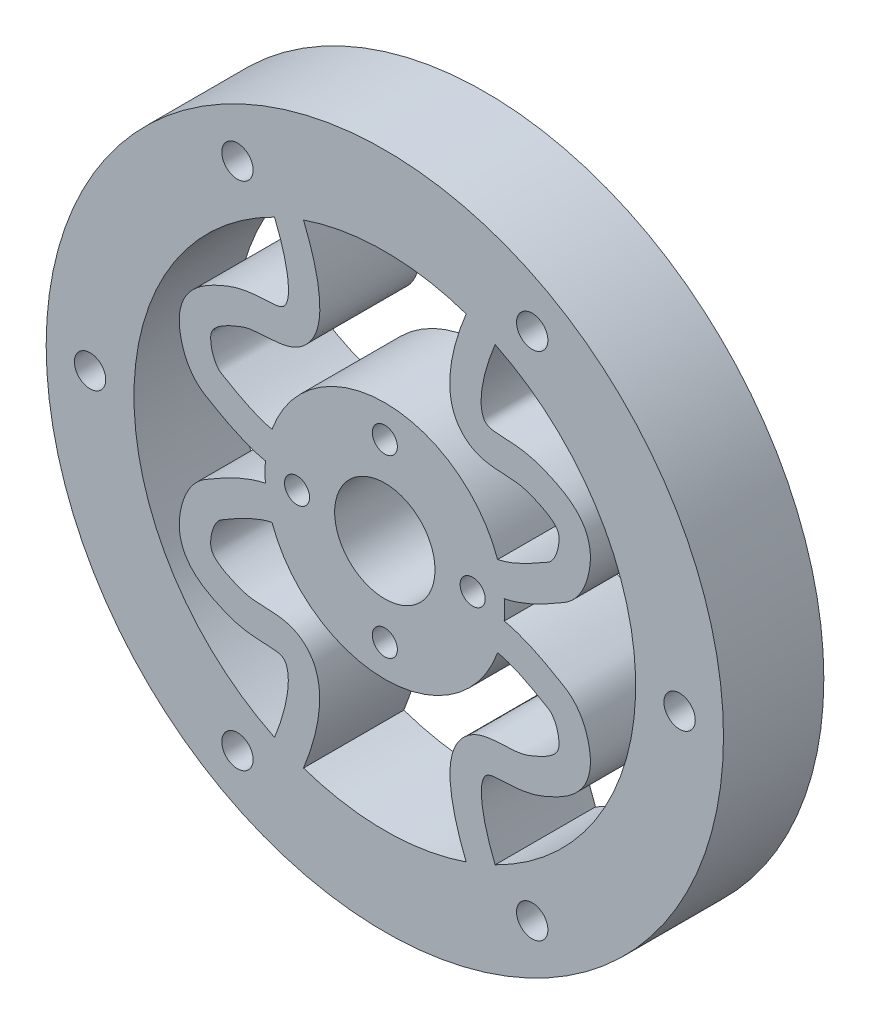
SolidWorks part; units mm, degrees
note: '?' marks a value the reader was unsure of.
ref_plane "Front Plane" through (0, 0, 0) normal (0, 0, 1) x (1, 0, 0)
ref_plane "Top Plane" through (0, 0, 0) normal (0, 1, 0) x (1, 0, 0)
ref_plane "Right Plane" through (0, 0, 0) normal (1, 0, 0) x (0, 0, -1)
sketch "Sketch1" plane through (0, 0, 0) normal (0, 0, 1) x (1, 0, 0)
  line L0 (0, 0) -> (18.4664, 44.5819) construction
  line L1 (0, -55) -> (0, 55) construction
  line L2 (0, 0) -> (47.1742, 10.1563) construction
  line L3 (55, 0) -> (-55, 0) construction
  circle A0 centre (0, 0) radius 27
  circle A2 centre (0, 0) radius 23.5 construction
  circle A4 centre (0, 0) radius 4
  circle A6 centre (0, 0) radius 7 construction
  circle A7 centre (0, 7) radius 1
  circle A11 centre (7, 0) radius 1
  circle A12 centre (0, -7) radius 1
  circle A13 centre (-7, 0) radius 1
  arc A23 (-9.5192, 0.7707) -> (-9.5192, -0.7707) centre (0, 0) ccw
  arc A24 (-8.9929, -3.2153) -> (8.9929, -3.2153) centre (0, 0) ccw
  circle A25 centre (23.5, 0) radius 1.25
  circle A26 centre (-11.75, -20.3516) radius 1.25
  circle A27 centre (-11.75, 20.3516) radius 1.25
  arc A28 (9.5192, -0.7707) -> (9.5192, 0.7707) centre (0, 0) ccw
  arc A29 (9.3366, 2.0095) -> (9.3364, 2.0101) centre (0, 0) ccw
  arc A30 (8.9929, 3.2153) -> (-8.9929, 3.2153) centre (0, 0) ccw
  arc A31 (-8.7929, 17.9635) -> (-8.793, -17.9635) centre (0, 0) ccw
  arc A32 (6.4833, 18.9201) -> (-6.4827, 18.9203) centre (0, 0) ccw
  arc A33 (8.7933, 17.9632) -> (8.793, -17.9635) centre (0, 0) cw
  arc A34 (-6.4828, -18.9202) -> (6.4828, -18.9202) centre (0, 0) ccw
  circle A44 centre (11.75, -20.3516) radius 1.25
  circle A45 centre (-23.5, 0) radius 1.25
  circle A46 centre (11.75, 20.3516) radius 1.25
  spline S0 degree 3 poles (7.6387, 18.4415) (6.8924, 16.6398) (4.5503, 10.0913) (10.6229, 10.7137) (13.2154, 9.739) (15.0461, 8.7572) (15.2048, 6.2073) (14.5676, 4.4635) (13.1737, 3.7046) (10.8346, 2.3086) (9.2384, 1.989) knots 0 0 0 0 0.486343 0.616567 0.651203 0.798071 0.829625 0.935186 0.953543 1 1 1 1 construction
  spline S1 degree 1 poles (6.4833, 18.9201) (8.9929, 3.2153) knots 0 0 1 1 construction
  spline S2 degree 3 poles (6.4833, 18.9201) (6.427, 18.7842) (6.3239, 18.5292) (6.0732, 17.8713) (5.7448, 16.9071) (5.3915, 15.578) (5.1644, 14.1619) (5.1614, 12.716) (5.5308, 11.2563) (6.4252, 10.1679) (7.4578, 9.6386) (8.3425, 9.4371) (9.1573, 9.3805) (9.9318, 9.3467) (10.6594, 9.2784) (11.2285, 9.1546) (11.9275, 8.8811) (12.6358, 8.5631) (13.212, 8.2219) (13.6136, 7.8734) (13.8118, 7.5652) (13.8949, 7.2813) (13.8776, 6.6399) (13.7286, 6.0587) (13.5501, 5.6523) (13.3952, 5.3961) (13.2639, 5.2382) (13.1592, 5.1431) (13.1005, 5.098) (12.9781, 5.0216) (12.5764, 4.793) (11.7235, 4.2916) (10.6004, 3.7308) (9.6522, 3.3777) (9.2193, 3.2606) (8.9929, 3.2153) knots 0 0 0 0 0.03125 0.0625 0.125 0.1875 0.25 0.3125 0.375 0.4375 0.46875 0.5 0.53125 0.5625 0.59375 0.625 0.65625 0.6875 0.71875 0.75 0.78125 0.8125 0.84375 0.875 0.890625 0.90625 0.921875 0.929688 0.9375 0.945312 0.953125 0.96875 0.984375 0.992188 1 1 1 1
  spline S3 degree 1 poles (8.7933, 17.9632) (9.4838, 0.7636) knots 0 0 1 1 construction
  spline S4 degree 3 poles (8.7933, 17.9632) (8.7432, 17.8422) (8.6515, 17.6154) (8.428, 17.0288) (8.138, 16.1766) (7.838, 15.0434) (7.6635, 13.9303) (7.6724, 12.9748) (7.8684, 12.3597) (8.0943, 12.1191) (8.4398, 11.947) (9.2686, 11.8775) (10.0711, 11.8423) (10.9838, 11.7683) (12.0309, 11.5334) (12.8911, 11.188) (14.0437, 10.6735) (15.2235, 9.924) (16.1267, 8.6625) (16.4326, 7.4181) (16.3602, 6.2658) (16.0676, 5.0803) (15.5954, 4.134) (15.105, 3.5353) (14.7733, 3.2271) (14.4869, 3.0121) (14.2128, 2.8471) (13.8389, 2.6348) (12.9315, 2.1011) (11.3827, 1.3224) (10.1517, 0.9006) (9.5075, 0.7683) (9.4924, 0.7653) (9.4838, 0.7636) knots 0 0 0 0 0.03125 0.0625 0.125 0.1875 0.25 0.3125 0.375 0.4375 0.5 0.53125 0.5625 0.59375 0.625 0.65625 0.6875 0.75 0.78125 0.8125 0.84375 0.875 0.90625 0.921875 0.929688 0.9375 0.945312 0.953125 0.96875 0.984375 0.999643 0.999786 1 1 1 1 only from (8.7933, 17.9632) to (9.5192, 0.7707)
  spline S5 degree 3 poles (8.793, -17.9635) (8.7898, -17.9556) (8.7565, -17.8739) (8.6747, -17.6688) (8.4731, -17.1392) (8.1815, -16.2822) (7.8733, -15.1269) (7.6879, -13.9816) (7.6865, -12.9892) (7.8819, -12.3408) (8.105, -12.1021) (8.4267, -11.9366) (9.2553, -11.8741) (10.0614, -11.8472) (10.98, -11.7813) (12.0373, -11.5491) (12.9008, -11.2007) (14.0538, -10.6818) (15.2308, -9.9254) (16.1285, -8.6624) (16.4333, -7.4204) (16.3614, -6.2674) (16.0685, -5.0818) (15.5963, -4.1354) (15.1061, -3.5367) (14.7744, -3.2284) (14.4881, -3.0134) (14.2141, -2.8483) (13.84, -2.636) (12.9323, -2.1019) (11.3829, -1.3228) (10.1546, -0.9017) (9.5221, -0.7713) (9.5192, -0.7707) knots 0.008785 0.008785 0.008785 0.008785 0.010978 0.03125 0.0625 0.125 0.1875 0.25 0.3125 0.375 0.4375 0.5 0.53125 0.5625 0.59375 0.625 0.65625 0.6875 0.75 0.78125 0.8125 0.84375 0.875 0.90625 0.921875 0.929688 0.9375 0.945312 0.953125 0.96875 0.984375 0.999645 0.999715 0.999715 0.999715 0.999715
  spline S6 degree 3 poles (6.4828, -18.9202) (6.4796, -18.9124) (6.4405, -18.8166) (6.3467, -18.5817) (6.1181, -17.9808) (5.7889, -17.0142) (5.4289, -15.6689) (5.1911, -14.2305) (5.1747, -12.7622) (5.5238, -11.2837) (6.4092, -10.1674) (7.4536, -9.6256) (8.3495, -9.426) (9.1698, -9.377) (9.9472, -9.3512) (10.6747, -9.2891) (11.2367, -9.1697) (11.9316, -8.8971) (12.6372, -8.5776) (13.2114, -8.2342) (13.6127, -7.8831) (13.8126, -7.5707) (13.8964, -7.2826) (13.8792, -6.6424) (13.7301, -6.0607) (13.5514, -5.654) (13.3964, -5.3976) (13.265, -5.2395) (13.1603, -5.1443) (13.1016, -5.0992) (12.9794, -5.0228) (12.5777, -4.7942) (11.7245, -4.2925) (10.6008, -3.7312) (9.6523, -3.3778) (9.2193, -3.2607) (8.9929, -3.2153) knots 0.007767 0.007767 0.007767 0.007767 0.009703 0.03125 0.0625 0.125 0.1875 0.25 0.3125 0.375 0.4375 0.46875 0.5 0.53125 0.5625 0.59375 0.625 0.65625 0.6875 0.71875 0.75 0.78125 0.8125 0.84375 0.875 0.890625 0.90625 0.921875 0.929688 0.9375 0.945312 0.953125 0.96875 0.984375 0.992188 1 1 1 1
  spline S7 degree 3 poles (-6.4828, -18.9202) (-6.4796, -18.9124) (-6.4405, -18.8166) (-6.3467, -18.5817) (-6.1181, -17.9808) (-5.7889, -17.0142) (-5.4289, -15.6689) (-5.1911, -14.2305) (-5.1747, -12.7622) (-5.5238, -11.2837) (-6.4092, -10.1674) (-7.4536, -9.6256) (-8.3495, -9.426) (-9.1698, -9.377) (-9.9472, -9.3512) (-10.6747, -9.2891) (-11.2367, -9.1697) (-11.9316, -8.8971) (-12.6372, -8.5776) (-13.2114, -8.2342) (-13.6127, -7.8831) (-13.8126, -7.5707) (-13.8964, -7.2826) (-13.8792, -6.6424) (-13.7301, -6.0607) (-13.5514, -5.654) (-13.3964, -5.3976) (-13.265, -5.2395) (-13.1603, -5.1443) (-13.1016, -5.0992) (-12.9794, -5.0228) (-12.5777, -4.7942) (-11.7245, -4.2925) (-10.6008, -3.7312) (-9.6523, -3.3778) (-9.2193, -3.2607) (-8.9929, -3.2153) knots 0.007767 0.007767 0.007767 0.007767 0.009703 0.03125 0.0625 0.125 0.1875 0.25 0.3125 0.375 0.4375 0.46875 0.5 0.53125 0.5625 0.59375 0.625 0.65625 0.6875 0.71875 0.75 0.78125 0.8125 0.84375 0.875 0.890625 0.90625 0.921875 0.929688 0.9375 0.945312 0.953125 0.96875 0.984375 0.992188 1 1 1 1
  spline S8 degree 3 poles (-8.793, -17.9635) (-8.7898, -17.9556) (-8.7565, -17.8739) (-8.6747, -17.6688) (-8.4731, -17.1392) (-8.1815, -16.2822) (-7.8733, -15.1269) (-7.6879, -13.9816) (-7.6865, -12.9892) (-7.8819, -12.3408) (-8.105, -12.1021) (-8.4267, -11.9366) (-9.2553, -11.8741) (-10.0614, -11.8472) (-10.98, -11.7813) (-12.0373, -11.5491) (-12.9008, -11.2007) (-14.0538, -10.6818) (-15.2308, -9.9254) (-16.1285, -8.6624) (-16.4333, -7.4204) (-16.3614, -6.2674) (-16.0685, -5.0818) (-15.5963, -4.1354) (-15.1061, -3.5367) (-14.7744, -3.2284) (-14.4881, -3.0134) (-14.2141, -2.8483) (-13.84, -2.636) (-12.9323, -2.1019) (-11.3829, -1.3228) (-10.1546, -0.9017) (-9.5221, -0.7713) (-9.5192, -0.7707) knots 0.008785 0.008785 0.008785 0.008785 0.010978 0.03125 0.0625 0.125 0.1875 0.25 0.3125 0.375 0.4375 0.5 0.53125 0.5625 0.59375 0.625 0.65625 0.6875 0.75 0.78125 0.8125 0.84375 0.875 0.90625 0.921875 0.929688 0.9375 0.945312 0.953125 0.96875 0.984375 0.999645 0.999715 0.999715 0.999715 0.999715
  spline S9 degree 3 poles (-8.7929, 17.9635) (-8.7916, 17.9601) (-8.7503, 17.8597) (-8.6583, 17.6314) (-8.4417, 17.063) (-8.1495, 16.2051) (-7.8463, 15.0637) (-7.6688, 13.942) (-7.6753, 12.9781) (-7.8711, 12.3565) (-8.096, 12.1169) (-8.4367, 11.946) (-9.2654, 11.8779) (-10.0686, 11.8443) (-10.9824, 11.7718) (-12.0316, 11.5374) (-12.8924, 11.1914) (-14.0452, 10.6761) (-15.2246, 9.9252) (-16.1269, 8.6633) (-16.4327, 7.4192) (-16.3604, 6.2667) (-16.0678, 5.0811) (-15.5956, 4.1346) (-15.105, 3.5358) (-14.7732, 3.2275) (-14.4867, 3.0125) (-14.2127, 2.8475) (-13.8389, 2.6353) (-12.9316, 2.1015) (-11.3829, 1.3226) (-10.1547, 0.9016) (-9.5221, 0.7713) (-9.5192, 0.7707) knots 0.003708 0.003708 0.003708 0.003708 0.004635 0.03125 0.0625 0.125 0.1875 0.25 0.3125 0.375 0.4375 0.5 0.53125 0.5625 0.59375 0.625 0.65625 0.6875 0.75 0.78125 0.8125 0.84375 0.875 0.90625 0.921875 0.929688 0.9375 0.945312 0.953125 0.96875 0.984375 0.999645 0.999716 0.999716 0.999716 0.999716
  spline S10 degree 3 poles (-6.4827, 18.9203) (-6.4814, 18.9169) (-6.4344, 18.8029) (-6.3307, 18.5454) (-6.087, 17.906) (-5.7565, 16.9368) (-5.4003, 15.6008) (-5.1701, 14.1782) (-5.1639, 12.7266) (-5.5289, 11.2626) (-6.4216, 10.1686) (-7.4564, 9.637) (-8.3431, 9.4359) (-9.159, 9.3808) (-9.934, 9.3485) (-10.6616, 9.2813) (-11.2294, 9.1584) (-11.9277, 8.885) (-12.6355, 8.5668) (-13.2114, 8.2251) (-13.6131, 7.8761) (-13.8117, 7.567) (-13.895, 7.2821) (-13.8777, 6.6407) (-13.7287, 6.0594) (-13.5502, 5.653) (-13.3952, 5.3968) (-13.2639, 5.2388) (-13.1592, 5.1437) (-13.1005, 5.0986) (-12.9779, 5.022) (-12.5761, 4.7933) (-11.7233, 4.2918) (-10.6003, 3.7309) (-9.6522, 3.3777) (-9.2193, 3.2606) (-8.9929, 3.2153) knots 0.003301 0.003301 0.003301 0.003301 0.004127 0.03125 0.0625 0.125 0.1875 0.25 0.3125 0.375 0.4375 0.46875 0.5 0.53125 0.5625 0.59375 0.625 0.65625 0.6875 0.71875 0.75 0.78125 0.8125 0.84375 0.875 0.890625 0.90625 0.921875 0.929688 0.9375 0.945312 0.953125 0.96875 0.984375 0.992188 1 1 1 1
  point P31 (0, 0)
  dimension "D1" = 54
  dimension "D3" = 3.5
  dimension "D4" = 2.5
  dimension "D5" = 8
  dimension "D6" = 3
  dimension "D8" = 2
  dimension "D11" = 22.5
  dimension "D12" = 55.35
  dimension "D10" = 4
extrude "Boss-Extrude1" add sketch "Sketch1" along normal blind 8
fillet "Fillet1" [suppressed] radius 1
ref_axis "Axis1" through (0, 0, 8) along (0, 0, -1)?
